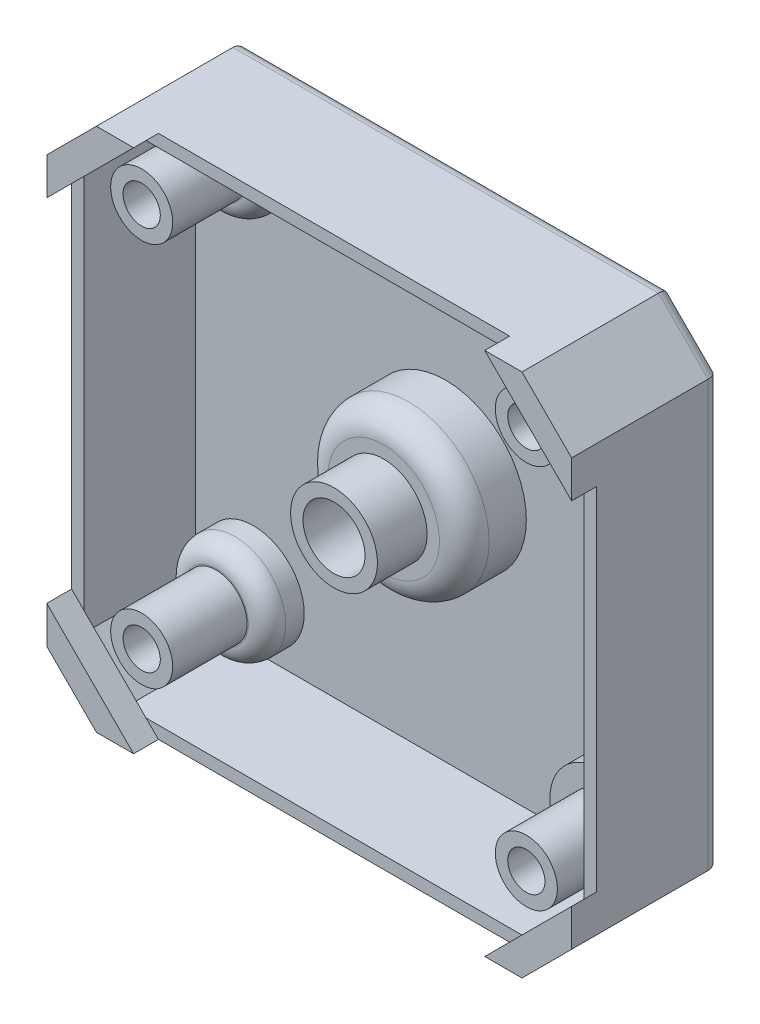
SolidWorks part; units mm, degrees
material "Plain Carbon Steel"
ref_plane "Alzado" through (0, 0, 0) normal (0, 0, 1) x (1, 0, 0)
ref_plane "Planta" through (0, 0, 0) normal (0, 1, 0) x (1, 0, 0)
ref_plane "Vista lateral" through (0, 0, 0) normal (1, 0, 0) x (0, 0, -1)
sketch "Croquis1" plane through (0, 0, 0) normal (0, 0, 1) x (1, 0, 0)
  line L0 (-17.15, 21.15) -> (-21.15, 17.15)
  line L1 (-17.15, 21.15) -> (17.15, 21.15)
  line L2 (-21.15, 17.15) -> (-21.15, -17.15)
  line L3 (-17.15, -21.15) -> (17.15, -21.15)
  line L4 (21.15, 17.15) -> (21.15, -17.15)
  line L5 (-21.15, 21.15) -> (21.15, -21.15) construction
  line L6 (-21.15, -21.15) -> (21.15, 21.15) construction
  line L7 (-21.15, -17.15) -> (-17.15, -21.15)
  line L8 (17.15, -21.15) -> (21.15, -17.15)
  line L9 (17.15, 21.15) -> (21.15, 17.15)
  point P0 (0, 0)
  dimension "D1" = 42.3
  dimension "D2" = 42.3
extrude "Saliente-Extruir4" add sketch "Croquis1" along normal blind 12
sketch "Croquis4" plane through (0, 0, 12) normal (0, 0, 1) x (1, 0, 0)
  line L0 (-21.15, 14.15) -> (-14.15, 21.15)
  line L1 (-14.15, 21.15) -> (14.15, 21.15)
  line L2 (-21.15, 14.15) -> (-21.15, -14.15)
  line L3 (-14.15, -21.15) -> (14.15, -21.15)
  line L4 (21.15, 14.15) -> (21.15, -14.15)
  line L5 (-21.15, 21.15) -> (21.15, -21.15) construction
  line L6 (-21.15, -21.15) -> (21.15, 21.15) construction
  line L7 (-21.15, -14.15) -> (-14.15, -21.15)
  line L8 (14.15, -21.15) -> (21.15, -14.15)
  line L9 (14.15, 21.15) -> (21.15, 14.15)
  point P0 (0, 0)
  dimension "D1" = 42.3
  dimension "D2" = 42.3
extrude "Cortar-Extruir1" cut sketch "Croquis4" against normal blind 2
sketch "Croquis5" plane through (0, 0, 0) normal (0, 0, -1) x (-1, 0, 0)
  circle A0 centre (-15.5, 15.5) radius 1.5
  circle A1 centre (15.5, 15.5) radius 1.5
  circle A2 centre (15.5, -15.5) radius 1.5
  circle A3 centre (-15.5, -15.5) radius 1.5
  point P12 (0, 0)
  dimension "D1" = 3
  dimension "D2" = 15.5
  dimension "D3" = 15.5
  dimension "D5" = 31
  dimension "D6" = 15.5
  dimension "D4" = 4
extrude "Cortar-Extruir2" cut sketch "Croquis5" against normal blind 22
sketch "Croquis6" plane through (0, 0, 0) normal (0, 0, -1) x (-1, 0, 0)
  circle A0 centre (0, 0) radius 5.5
  dimension "D1" = 11
extrude "Cortar-Extruir3" cut sketch "Croquis6" against normal blind 5
fillet "Redondeo1" radius 1 10 edges at (-5.5, 0, 5) (-19.15, 19.15, 0) (-19.15, -19.15, 0) (-21.15, 0, 0) (0, -21.15, 0) (19.15, -19.15, 0) (21.15, 0, 0) (19.15, 19.15, 0) (0, 21.15, 0) (-5.5, 0, 0)
sketch "Croquis7" plane through (0, 0, 0) normal (0, 0, -1) x (-1, 0, 0)
  circle A0 centre (-15.5, 15.5) radius 3.1
  circle A1 centre (15.5, 15.5) radius 3.1
  circle A2 centre (15.5, -15.5) radius 3.1
  circle A3 centre (-15.5, -15.5) radius 3.1
  point P11 (0, 0)
  dimension "D1" = 6.2
  dimension "D3" = 15.5
  dimension "D4" = 15.5
  dimension "D2" = 4
extrude "Cortar-Extruir4" cut sketch "Croquis7" against normal blind 3
fillet "Redondeo2" radius 0.5 7 edges at (12.4, -15.5, 0) (-18.6, -15.5, 3) (-18.6, -15.5, 0) (-18.6, 15.5, 3) (-18.6, 15.5, 0) (12.4, 15.5, 3) (12.4, 15.5, 0)
sketch "Croquis8" plane through (0, 0, 0) normal (0, 0, -1) x (-1, 0, 0)
  circle A0 centre (0, 0) radius 2.5
  dimension "D1" = 5
extrude "Cortar-Extruir5" cut sketch "Croquis8" against normal blind 22
shell "Shell2" thickness 1 removed face at (-2.5, 0, 10)
